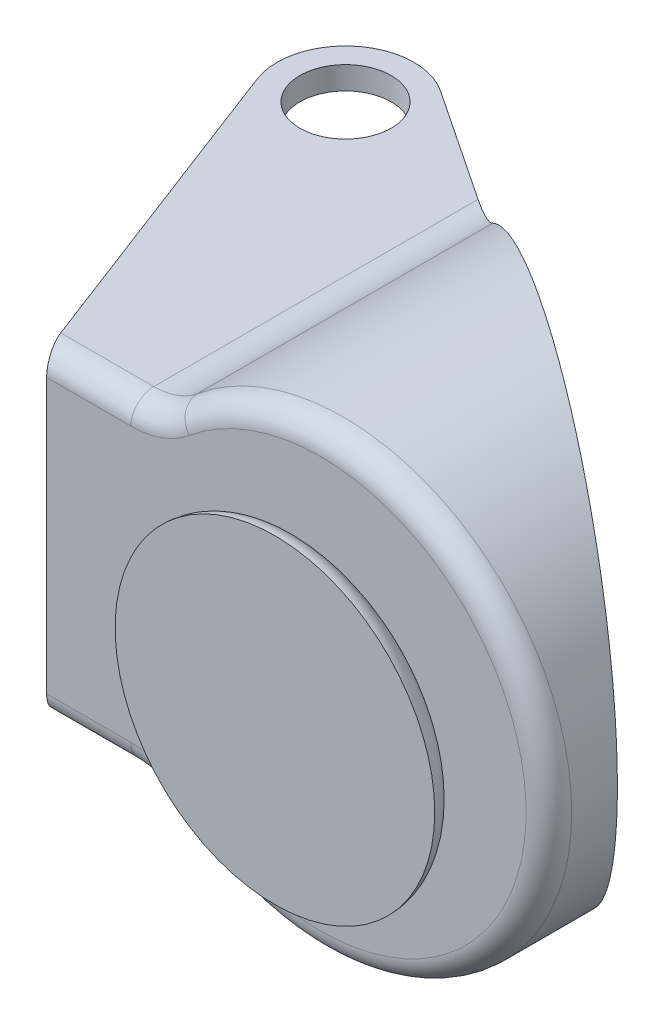
SolidWorks part; units mm, degrees
ref_plane "前视基准面" through (0, 0, 0) normal (0, 0, 1) x (1, 0, 0)
ref_plane "上视基准面" through (0, 0, 0) normal (0, 1, 0) x (1, 0, 0)
ref_plane "右视基准面" through (0, 0, 0) normal (1, 0, 0) x (0, 0, -1)
sketch "草图1" plane through (0, 0, 0) normal (0, 0, 1) x (1, 0, 0)
  circle A0 centre (0, 0) radius 10
  dimension "D1" = 20
extrude "凸台-拉伸1" add sketch "草图1" along normal blind 14
sketch "草图3" plane through (0, 0, 0) normal (0, 1, 0) x (1, 0, 0)
  line L0 (-8, 0) -> (10, 0)
  line L1 (10, 0) -> (10, -12)
  line L2 (10, -14) -> (10, 0) construction
  line L3 (10, -12) -> (-8, 0)
  dimension "D1" = 12
  dimension "D2" = 18
extrude "切除-拉伸1" cut sketch "草图3" against normal mid plane 1000
sketch "草图4" plane through (0, 0, 14) normal (0, 0, 1) x (1, 0, 0)
  circle A0 centre (0, 0) radius 8
  dimension "D1" = 16
extrude "切除-拉伸2" cut sketch "草图4" against normal blind 1000
sketch "草图6" plane through (0, 0, 14) normal (0, 0, 1) x (1, 0, 0)
  circle A0 centre (0, 0) radius 10
extrude "凸台-拉伸2" add sketch "草图6" along normal blind 1
sketch "草图5" plane through (0, 0, 0) normal (0, 1, 0) x (1, 0, 0)
  line L0 (-6, -15) -> (-12, -15)
  line L2 (-7.8316, -0.1122) -> (-13.2442, 3.4962) construction
  line L4 (-12, -15) -> (-17.7103, -0.0718)
  line L5 (8, -10.6667) -> (-8, 0) construction
  line L6 (10, -12) -> (-8, 0) construction
  line L8 (-11.8596, 2.5731) -> (-6.6154, -0.9231) construction
  line L9 (-13.2442, 3.4962) -> (-6, -1.3333)
  line L10 (-6, -1.3333) -> (-6, -15)
  arc A0 (-13.2442, 3.4962) -> (-17.7103, -0.0718) centre (-14.9083, 1) ccw
  circle A1 centre (-14.9083, 1) radius 2
  dimension "D3" = 4
  dimension "D4" = 6
  dimension "D1" = 6
  dimension "D6" = 16
extrude "凸台-拉伸3" add sketch "草图5" along normal mid plane 14
extrude "切除-拉伸3" cut sketch "草图5<2>" against normal mid plane 12
sketch "草图5<2>" plane through (0, 0, 0) normal (0, 1, 0) x (1, 0, 0) same geometry as "草图5"
sketch "草图7" plane through (-6, 0, 0) normal (-1, 0, 0) x (0, 0, 1)
  line L0 (15, -6) -> (1.3333, -6) construction
  line L1 (15, 6) -> (14, 6)
  line L2 (15, 6) -> (15, -6)
  line L3 (15, -6) -> (14, -6)
  line L4 (14, 6) -> (14, -6)
  line L5 (14, 5.2915) -> (14, -5.2915) construction
extrude "凸台-拉伸4" add sketch "草图7" along normal blind 5
sketch "草图8" plane through (0, 6, 0) normal (0, -1, 0) x (1, 0, 0)
  line L0 (-12, 15) -> (-12.3825, 14)
  line L1 (-17.7103, 0.0718) -> (-12, 15) construction
  line L2 (-12.3825, 14) -> (-11, 14)
  line L3 (-11, 14) -> (-11, 15)
  line L4 (-11, 15) -> (-12, 15)
  line L5 (-11, 14) -> (-6, 14) construction
extrude "凸台-拉伸5" add sketch "草图8" along normal blind 12
sketch "草图9" plane through (-6, 0, 0) normal (-1, 0, 0) x (0, 0, 1)
  line L1 (1.3333, -6) -> (14, -6)
  line L2 (1.3333, -6) -> (1.3333, 6)
  line L3 (1.3333, 6) -> (14, 6)
  line L4 (14, -6) -> (14, 6)
extrude "切除-拉伸4" cut sketch "草图9" against normal blind 5
sketch "草图10" plane through (0, 0, 15) normal (0, 0, 1) x (1, 0, 0)
  circle A0 centre (0, 0) radius 4
  dimension "D1" = 8
extrude "凸台-拉伸6" add sketch "草图10" along normal blind 2
sketch "草图11" plane through (0, 0, 17) normal (0, 0, 1) x (1, 0, 0)
  circle A0 centre (0, 0) radius 7
  dimension "D1" = 14
extrude "凸台-拉伸7" add sketch "草图11" against normal blind 1
fillet "圆角1" radius 3 4 edges at (-5.2915, -6, 7.9028) (-5.2915, 6, 7.9028) (-7.1414, -7, 7.7862) (-7.1414, 7, 7.7862)
fillet "圆角2" radius 1 1 edges at (7, 0, 16)
fillet "圆角4" radius 1 5 edges at (-10.1533, -7, 15) (-7.2876, -7.1784, 15) (-10.1533, 7, 15) (-7.2876, 7.1784, 15) (10, 0, 15)
